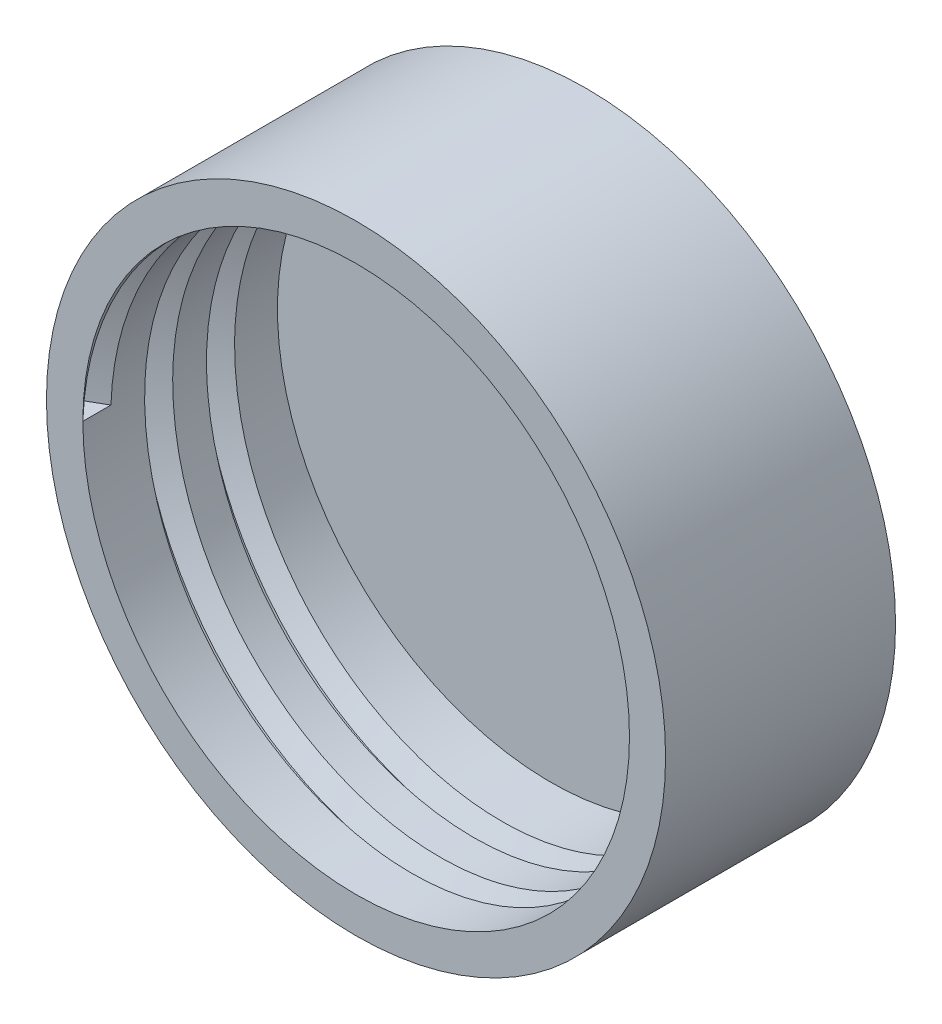
SolidWorks part; units mm, degrees
ref_plane "Front Plane" through (0, 0, 0) normal (0, 0, 1) x (1, 0, 0)
ref_plane "Top Plane" through (0, 0, 0) normal (0, 1, 0) x (1, 0, 0)
ref_plane "Right Plane" through (0, 0, 0) normal (1, 0, 0) x (0, 0, -1)
sketch "Sketch1" plane through (0, 0, 0) normal (0, 0, 1) x (1, 0, 0)
  circle A0 centre (-0.3717, 0.1859) radius 17.5
extrude "Boss-Extrude3" add sketch "Sketch1" along normal blind 13
sketch "Sketch7" plane through (0, 0, 13) normal (0, 0, 1) x (1, 0, 0)
  circle A0 centre (-0.3628, 0.1572) radius 15.45
extrude "Cut-Extrude2" cut sketch "Sketch7" against normal blind 11
thread "Thread1" pitch 2.1167 method cut profile "Thread Profile1" start angle 0, offset 0, length 0, pitch 3.5, diameter 30.9
ref_plane "Plane1" through (-15.8128, 0.1572, 13) normal (0, -1, 0) x (-1, 0, 0)
sketch "Thread Profile1" plane through (-15.8128, 0.1572, 13) normal (0, -1, 0) x (-1, 0, 0)
  line L0 (0, 0) -> (0, 2.1167) construction
  line L1 (0, 0) -> (1.1457, 0.6615)
  line L2 (1.1457, 0.6615) -> (1.1457, 0.926)
  line L3 (1.1457, 0.926) -> (0, 1.5875)
  line L4 (1.1457, 0.7937) -> (0, 0.7937) construction
  line L11 (0, 0) -> (0, 1.5875)
  point P2 (0, 0)
  dimension "Pitch" = 2.1167
  dimension "Profile_Angle" = 60
  dimension "Profile_Land" = 0.2646
  dimension "Profile_Height" = 1.1457
